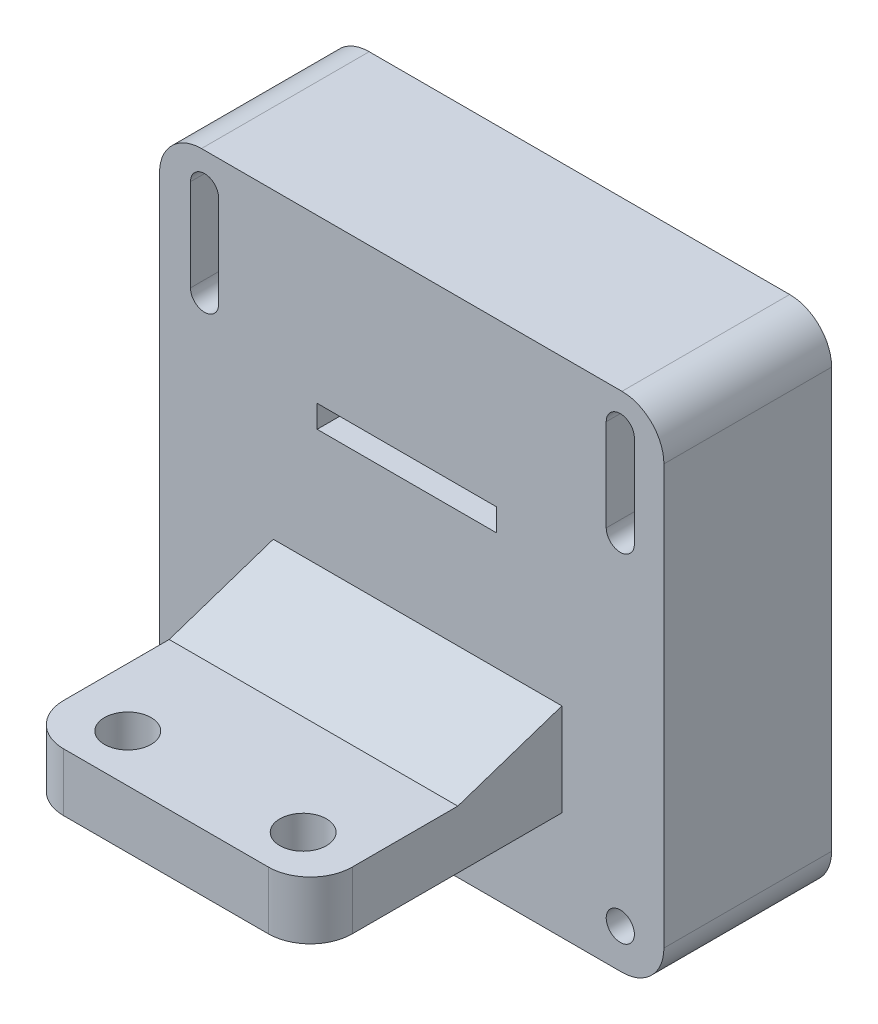
SolidWorks part; units mm, degrees
ref_plane "Alzado" through (0, 0, 0) normal (0, 0, 1) x (1, 0, 0)
ref_plane "Planta" through (0, 0, 0) normal (0, 1, 0) x (1, 0, 0)
ref_plane "Vista lateral" through (0, 0, 0) normal (1, 0, 0) x (0, 0, -1)
sketch "Croquis1" plane through (0, 0, 0) normal (0, 0, 1) x (1, 0, 0)
  line L0 (-21.7038, 24.1707) -> (-21.7038, 13.2033) construction
  line L1 (-27.0724, 28.25) -> (33.0729, 28.25)
  line L2 (-27.0724, 28.25) -> (-27.0724, -31.75)
  line L3 (-27.0724, -31.75) -> (33.0729, -31.75)
  line L4 (33.0729, 28.25) -> (33.0729, -31.75)
  line L5 (-8.2743, 8.8387) -> (13.1009, 8.8387)
  line L6 (-8.2743, 8.8387) -> (-8.2743, 6.1528)
  line L7 (-8.2743, 6.1528) -> (13.1009, 6.1528)
  line L8 (13.1009, 8.8387) -> (13.1009, 6.1528)
  line L9 (-20.0251, 24.1707) -> (-20.0251, 13.2033)
  line L10 (-23.3825, 24.1707) -> (-23.3825, 13.2033)
  line L11 (27.8733, 24.1707) -> (27.8733, 13.2033) construction
  line L12 (29.552, 24.1707) -> (29.552, 13.2033)
  line L13 (26.1946, 24.1707) -> (26.1946, 13.2033)
  circle A2 centre (27.8733, -27.0851) radius 1.6787
  circle A3 centre (-21.7038, -27.0851) radius 1.6787
  arc A4 (-20.0251, 24.1707) -> (-23.3825, 24.1707) centre (-21.7038, 24.1707) ccw
  arc A5 (-23.3825, 13.2033) -> (-20.0251, 13.2033) centre (-21.7038, 13.2033) ccw
  arc A6 (29.552, 24.1707) -> (26.1946, 24.1707) centre (27.8733, 24.1707) ccw
  arc A7 (26.1946, 13.2033) -> (29.552, 13.2033) centre (27.8733, 13.2033) ccw
  point P16 (-21.7038, 18.687)
  point P22 (27.8733, 18.687)
  dimension "D1" = 60.1453
  dimension "D2" = 60
extrude "Saliente-Extruir1" add sketch "Croquis1" along normal blind 20
sketch "Croquis2" plane through (0, 0, 20) normal (0, 0, 1) x (1, 0, 0)
  line L1 (-13.5067, -7.8196) -> (20.9094, -7.8196)
  line L2 (-13.5067, -7.8196) -> (-13.5067, -18.8667)
  line L3 (-13.5067, -18.8667) -> (20.9094, -18.8667)
  line L4 (20.9094, -7.8196) -> (20.9094, -18.8667)
extrude "Saliente-Extruir2" add sketch "Croquis2" along normal blind 30
sketch "Croquis3" plane through (20.9094, 0, 0) normal (1, 0, 0) x (0, 0, -1)
  line L0 (-32.4143, -11.9623) -> (-20, -7.8196)
  line L1 (-54.9335, -4.4205) -> (-32.4143, -4.4205)
  line L2 (-54.9335, -4.4205) -> (-54.9335, -11.9623)
  line L3 (-54.9335, -11.9623) -> (-32.4143, -11.9623)
  line L5 (-20, -7.8196) -> (-32.4143, -4.4205)
extrude "Cortar-Extruir1" cut sketch "Croquis3" against normal blind 50
sketch "Croquis4" plane through (0, -18.8667, 0) normal (0, -1, 0) x (1, 0, 0)
  circle A0 centre (-6.5237, 44.3331) radius 2.7788
  circle A1 centre (14.3869, 44.3331) radius 2.7788
extrude "Cortar-Extruir2" cut sketch "Croquis4" against normal blind 52
fillet "Redondeo1" radius 5 2 edges at (-13.5067, -15.4145, 50) (20.9094, -15.4145, 50)
fillet "Redondeo2" radius 5 4 edges at (-27.0724, 28.25, 10) (33.0729, 28.25, 10) (-27.0724, -31.75, 10) (33.0729, -31.75, 10)
